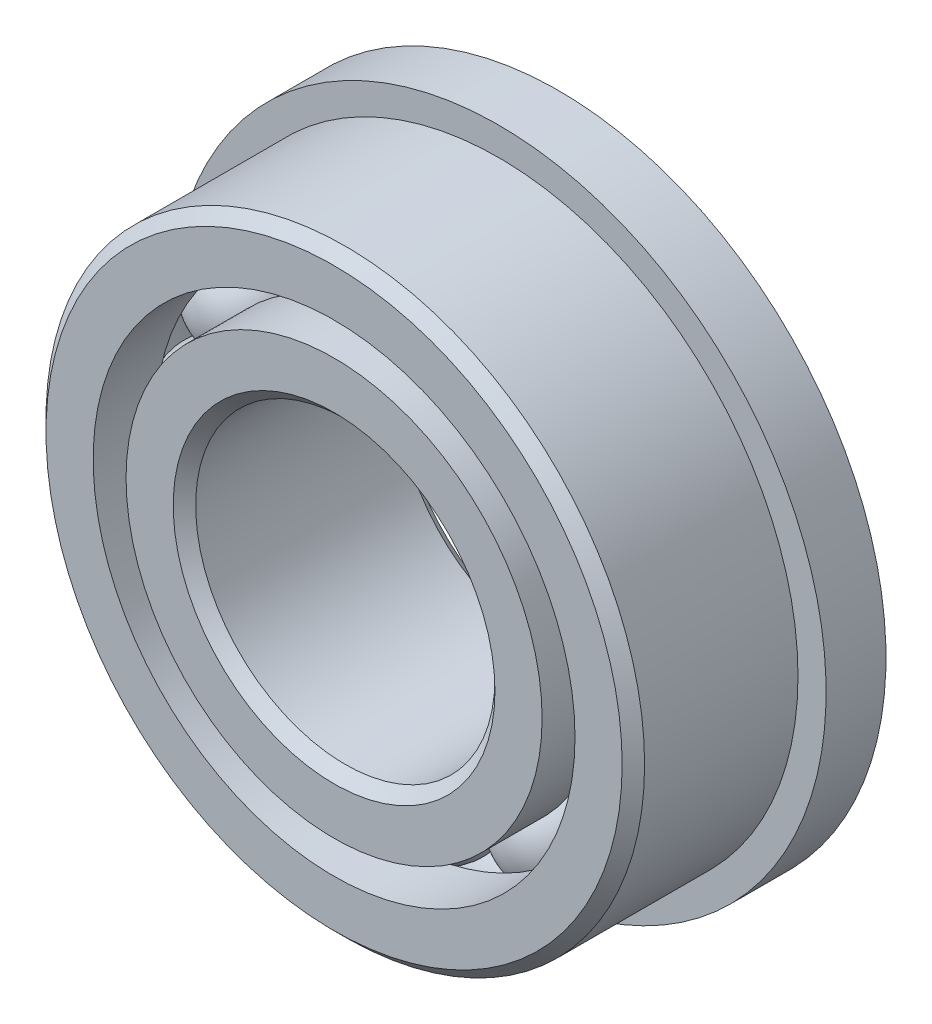
SolidWorks part; units mm, degrees
material "Cast Alloy Steel"
ref_plane "Front Plane" through (0, 0, 0) normal (0, 0, 1) x (1, 0, 0)
ref_plane "Top Plane" through (0, 0, 0) normal (0, 1, 0) x (1, 0, 0)
ref_plane "Right Plane" through (0, 0, 0) normal (1, 0, 0) x (0, 0, -1)
sketch "Sketch1" plane through (0, 0, 0) normal (1, 0, 0) x (0, 0, -1)
  line L0 (-2.3813, 0) -> (2.3813, 0) construction
  line L1 (0, 6.35) -> (0, -6.35) construction
  line L2 (2.1431, 6.35) -> (-2.1431, 6.35)
  line L3 (-2.1431, 6.35) -> (-2.3813, 6.1119)
  line L4 (-2.3813, 6.1119) -> (-2.3813, 5.1114)
  line L5 (-2.3813, 5.1114) -> (-1.0583, 5.1114)
  line L6 (2.3813, 5.1114) -> (1.0583, 5.1114)
  line L7 (2.3813, 6.1119) -> (2.3813, 5.1114)
  line L8 (2.1431, 6.35) -> (2.3813, 6.1119)
  line L9 (0, 6.35) -> (0, 4.7625) construction
  line L10 (0, 4.7625) -> (0, 3.175) construction
  arc A0 (-1.0583, 5.1114) -> (1.0583, 5.1114) centre (0, 4.7625) cw
  point P14 (0, 3.175)
  dimension "D3" = 2.1167
  dimension "D1" = 45
  dimension "Width" = 4.7625
  dimension "OD" = 12.7
  dimension "D2" = 0.2381
  dimension "Shaft Dia" = 6.35
  dimension "D4" = 0.3489
revolve "Revolve1" add sketch "Sketch1" angle 360 about L0
sketch "Sketch3" plane through (0, 0, 0) normal (1, 0, 0) x (0, 0, -1)
  line L0 (-2.1431, 6.35) -> (-2.3813, 6.1119) construction
  line L1 (-1.0583, 4.4136) -> (-2.3813, 4.4136)
  line L2 (-2.3813, 6.1119) -> (-2.3813, 5.1114) construction
  line L3 (-2.3813, 4.4136) -> (-2.3813, 3.4131)
  line L5 (-2.3813, 3.4131) -> (-2.1431, 3.175)
  line L6 (-2.1431, 3.175) -> (2.1431, 3.175)
  line L7 (2.3813, 6.1119) -> (2.3813, 5.1114) construction
  line L8 (2.1431, 3.175) -> (2.3813, 3.4131)
  line L10 (2.3813, 3.4131) -> (2.3813, 4.4136)
  line L11 (2.3813, 4.4136) -> (1.0583, 4.4136)
  line L13 (2.1431, 6.35) -> (2.3813, 6.1119) construction
  arc A1 (1.0583, 4.4136) -> (-1.0583, 4.4136) centre (0, 4.7625) cw
  arc A2 (1.0583, 5.1114) -> (-1.0583, 5.1114) centre (0, 4.7625) ccw construction
revolve "Revolve3" add sketch "Sketch3" angle 360 about L0
sketch "Sketch5" plane through (0, 0, 0) normal (1, 0, 0) x (0, 0, -1)
  line L0 (2.3813, 6.1119) -> (2.3813, 5.1114) construction
  line L1 (2.3813, 5.6116) -> (1.1113, 5.6116)
  line L2 (2.3813, 5.6116) -> (2.3813, 6.9469)
  line L3 (2.3813, 6.9469) -> (1.1113, 6.9469)
  line L4 (1.1113, 5.6116) -> (1.1113, 6.9469)
  line L5 (2.3813, 0) -> (-2.3813, 0) construction
  dimension "Th" = 1.27
  dimension "Flange OD" = 13.8938
revolve "Revolve5" add sketch "Sketch5" angle 360 about L5
sketch "Sketch4" plane through (0, 0, 0) normal (1, 0, 0) x (0, 0, -1)
  line L0 (-1.1144, 4.7625) -> (1.1144, 4.7625)
  arc A2 (-1.1144, 4.7625) -> (1.1144, 4.7625) centre (0, 4.7625) cw
  arc A3 (1.0583, 5.1114) -> (-1.0583, 5.1114) centre (0, 4.7625) ccw construction
revolve "Revolve4" add sketch "Sketch4" angle 360 about L0
ref_axis "Axis1" through (0, 0, -2.3813) along (0, 0, 1)
pattern_circular "CirPattern1" count 12 every 30 about axis through (0, 0, -2.3813) along (0, 0, 1) of bodies 104
equation "\"D2@Sketch1\" = \"Width@Sketch1\"*.05"
equation "\"D3@Sketch1\" = \"Width@Sketch1\"/2.25"
equation "\"D4@Sketch1\" = (((\"OD@Sketch1\"-\"Width@Sketch1\")/2)/3.25)/3.5"
equation "\"D2@CirPattern1\" = 360/\"Balls@CirPattern1\""
